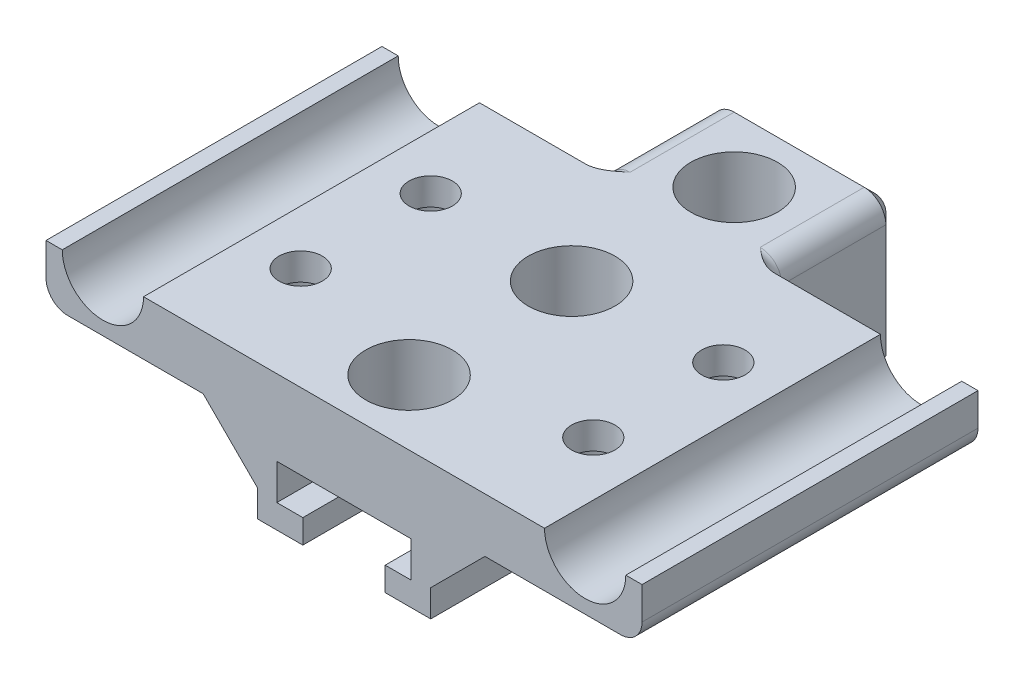
SolidWorks part; units mm, degrees
ref_plane "前基準面" through (0, 0, 0) normal (0, 0, 1) x (1, 0, 0)
ref_plane "上基準面" through (0, 0, 0) normal (0, 1, 0) x (1, 0, 0)
ref_plane "右基準面" through (0, 0, 0) normal (1, 0, 0) x (0, 0, -1)
sketch "草圖1" plane through (0, 0, 0) normal (0, 0, 1) x (1, 0, 0)
  line L1 (-8, 4) -> (8, 4)
  line L2 (-8, 4) -> (-8, -4)
  line L3 (-8, -4) -> (8, -4)
  line L4 (8, 4) -> (8, -4)
  point P4 (0, 4)
  point P7 (-8, 0)
  dimension "D1" = 16
  dimension "D2" = 8
extrude "填料-伸長1" add sketch "草圖1" along normal blind 43
sketch "草圖2" plane through (0, 0, 43) normal (0, 0, 1) x (1, 0, 0)
  line L1 (-6.2, 2) -> (6.2, 2)
  line L2 (-6.2, 2) -> (-6.2, -1.3)
  line L3 (-3.8, -4) -> (3.8, -4)
  line L4 (6.2, 2) -> (6.2, -1.3)
  line L5 (-8, -4) -> (8, -4) construction
  line L6 (-6.2, -1.3) -> (-3.8, -1.3)
  line L9 (-3.8, -1.3) -> (-3.8, -4)
  line L10 (6.2, -1.3) -> (3.8, -1.3)
  line L13 (3.8, -1.3) -> (3.8, -4)
  point P6 (0, 2)
  dimension "D1" = 12.4
  dimension "D2" = 6
  dimension "D3" = 2.4
  dimension "D4" = 2.4
  dimension "D5" = 2.7
  dimension "D6" = 2.7
  dimension "D7" = 3.3
extrude "除料-伸長1" cut sketch "草圖2" against normal through all
sketch "草圖4" plane through (0, 0, 43) normal (0, 0, 1) x (1, 0, 0)
  line L0 (8, 4) -> (-8, 4) construction
  line L1 (-27.5, 4) -> (27.5, 4)
  line L2 (-27.5, 4) -> (-27.5, 9)
  line L3 (-27.5, 9) -> (-26, 9)
  line L4 (27.5, 4) -> (27.5, 9)
  line L5 (-18.5, 9) -> (18.5, 9)
  line L6 (26, 9) -> (27.5, 9)
  arc A0 (-26, 9) -> (-18.5, 9) centre (-22.25, 9) ccw
  arc A1 (18.5, 9) -> (26, 9) centre (22.25, 9) ccw
  dimension "D3" = 7.5
  dimension "D4" = 7.5
  dimension "D1" = 55
  dimension "D2" = 5
extrude "填料-伸長2" add sketch "草圖4" against normal blind 31
fillet "圓角1" radius 2 2 edges at (-27.5, 4, 27.5) (27.5, 4, 27.5)
chamfer "導角1" distance 5 angle 45 2 edges at (8, 4, 27.5) (-8, 4, 27.5)
sketch "草圖5" plane through (0, 9, 0) normal (0, 1, 0) x (1, 0, 0)
  line L0 (-27.5, -12) -> (-27.5, -43) construction
  line L1 (27.5, -12) -> (27.5, -43) construction
  line L2 (-18.5, -27.5) -> (18.5, -27.5) construction
  line L3 (18.5, -43) -> (-18.5, -43) construction
  line L4 (-18.5, -12) -> (-18.5, -43) construction
  line L5 (18.5, -12) -> (18.5, -43) construction
  circle A0 centre (-13.5, -21.5) radius 2
  circle A1 centre (13.5, -21.5) radius 2
  circle A2 centre (13.5, -33.5) radius 2
  circle A3 centre (-13.5, -33.5) radius 2
  dimension "D1" = 4
  dimension "D2" = 4
  dimension "D3" = 14
  dimension "D4" = 14
  dimension "D5" = 21.5
  dimension "D6" = 21.5
extrude "除料-伸長3" cut sketch "草圖5" against normal through all
sketch "草圖6" plane through (0, 4, 0) normal (0, -1, 0) x (1, 0, 0)
  circle A0 centre (-13.5, 21.5) radius 3.75
  circle A1 centre (13.5, 21.5) radius 3.75
  circle A2 centre (13.5, 33.5) radius 3.75
  circle A3 centre (-13.5, 33.5) radius 3.75
  dimension "D1" = 7.5
  dimension "D2" = 7.5
  dimension "D3" = 7.5
  dimension "D4" = 7.5
extrude "除料-伸長4" cut sketch "草圖6" against normal blind 2.5 and the other way through all
sketch "草圖8" plane through (0, 0, 12) normal (0, 0, -1) x (-1, 0, 0)
  line L0 (-18.5, 9) -> (18.5, 9) construction
  line L1 (-8, 4) -> (8, 4)
  line L2 (-8, 4) -> (-8, 9)
  line L3 (-8, 9) -> (8, 9)
  line L4 (8, 4) -> (8, 9)
extrude "填料-伸長4" add sketch "草圖8" along normal up to surface (12 mm away) up to face at (0, -0.7667, 0)
sketch "草圖3" plane through (0, 9, 0) normal (0, 1, 0) x (1, 0, 0)
  circle A0 centre (0, -37) radius 4
  circle A1 centre (0, -22) radius 4
  circle A2 centre (0, -7) radius 4
  dimension "D1" = 8
  dimension "D3" = 3
extrude "除料-伸長2" cut sketch "草圖3" against normal blind 6.2
sketch "草圖10" plane through (0, 0, 43) normal (0, 0, 1) x (1, 0, 0)
  line L0 (-6.2, -1.3) -> (-3.8, -1.3) construction
  line L1 (-3.8, -4) -> (-8, -4)
  line L2 (-3.8, -4) -> (-3.8, -3.5)
  line L3 (-3.8, -3.5) -> (-8, -3.5)
  line L4 (-8, -4) -> (-8, -3.5)
  line L5 (3.8, -4) -> (8, -4)
  line L6 (3.8, -4) -> (3.8, -3.5)
  line L7 (3.8, -3.5) -> (8, -3.5)
  line L8 (8, -4) -> (8, -3.5)
  line L9 (3.8, -1.3) -> (6.2, -1.3) construction
  line L11 (-8, -1) -> (-8, -4) construction
  line L12 (8, -4) -> (8, -1) construction
  dimension "D1" = 2.2
  dimension "D2" = 2.2
extrude "除料-伸長5" cut sketch "草圖10" against normal through all
fillet "圓角2" radius 2 2 edges at (8, 9, 6) (-8, 9, 6)
chamfer "導角2" distance 1 angle 45 5 edges at (8, 1.75, 0) (-8, 1.75, 0) (7.4142, 8.4142, 0) (-7.4142, 8.4142, 0) (0, 9, 0)
fillet "圓角3" radius 1.4 4 edges at (7.4142, 8.4142, 12) (-7.4142, 8.4142, 12) (8, 3, 12) (-8, 3, 12)
sketch "草圖11" plane through (0, 0, 12) normal (0, 0, -1) x (-1, 0, 0)
  line L0 (-17.6, 5) -> (-10.6, 5) construction
  line L2 (-13, 4) -> (-25.5, 4) construction
  line L3 (-9.4, 0.4) -> (-9.4, 7) construction
  line L4 (0, 9) -> (0, 0) construction
  line L5 (-6, 9) -> (6, 9) construction
  line L6 (17.6, 5) -> (10.6, 5) construction
  line L7 (-13.6371, 7.16) -> (-13.6371, 8.2545)
  line L8 (15.5364, 7.6659) -> (16.1812, 5.9016)
  spline S0 degree 3 poles (-14.3217, 5.6792) (-14.3613, 5.5944) (-14.4274, 5.4735) (-14.525, 5.3224) (-14.5998, 5.2193) (-14.68, 5.1259) (-14.7882, 5.0123) (-14.878, 4.9386) (-14.94, 4.8946) knots 0 0 0 0 0.277898 0.408711 0.534276 0.656039 0.774144 1 1 1 1
  spline S1 degree 3 poles (-14.94, 4.8946) (-14.99, 4.8607) (-15.067, 4.8143) (-15.1749, 4.766) (-15.2555, 4.7357) (-15.3377, 4.7134) (-15.4487, 4.6913) (-15.5335, 4.6842) (-15.5902, 4.6846) knots 0 0 0 0 0.261398 0.38728 0.510792 0.633341 0.754911 1 1 1 1
  spline S2 degree 3 poles (-15.5902, 4.6846) (-15.667, 4.6851) (-15.7816, 4.6959) (-15.9282, 4.7374) (-16.0337, 4.7799) (-16.1355, 4.8345) (-16.2674, 4.9271) (-16.3577, 5.0104) (-16.413, 5.0726) knots 0 0 0 0 0.245474 0.365588 0.485789 0.608633 0.734185 1 1 1 1
  spline S3 degree 3 poles (-16.413, 5.0726) (-16.4864, 5.1498) (-16.5808, 5.2815) (-16.6806, 5.4755) (-16.74, 5.6355) (-16.7883, 5.8066) (-16.8331, 6.0584) (-16.8454, 6.2551) (-16.8455, 6.3895) knots 0 0 0 0 0.22456 0.340653 0.460058 0.584555 0.715943 1 1 1 1
  spline S4 degree 3 poles (-16.8455, 6.3895) (-16.8458, 6.523) (-16.8373, 6.7183) (-16.8036, 6.97) (-16.7682, 7.1431) (-16.7243, 7.3059) (-16.6528, 7.5051) (-16.5817, 7.6438) (-16.5278, 7.7299) knots 0 0 0 0 0.286836 0.419499 0.545655 0.666292 0.781656 1 1 1 1
  spline S5 degree 3 poles (-16.5278, 7.7299) (-16.4753, 7.8088) (-16.3891, 7.9209) (-16.2476, 8.0391) (-16.136, 8.1114) (-16.015, 8.166) (-15.84, 8.2208) (-15.7001, 8.234) (-15.6059, 8.2342) knots 0 0 0 0 0.259167 0.381557 0.501242 0.62064 0.742518 1 1 1 1
  spline S6 degree 3 poles (-15.6059, 8.2342) (-15.5447, 8.234) (-15.4227, 8.2202) (-15.3072, 8.1784) (-15.253, 8.1507) knots 0 0 0 0 0.501439 1 1 1 1
  spline S7 degree 3 poles (-15.253, 8.1507) (-15.2323, 8.1338) (-15.2068, 8.1071) (-15.174, 8.077) (-15.1582, 8.0594) (-15.1475, 8.0463) (-15.1417, 8.0391) (-15.1407, 8.0355) knots 0 0 0 0 0.465485 0.641944 0.776824 0.876731 0.937633 0.937633 0.937633 0.937633
  spline S8 degree 3 poles (-15.1407, 8.0355) (-15.1338, 8.0444) (-15.1164, 8.0704) (-15.0772, 8.1526) (-15.0487, 8.2267) (-15.0282, 8.2826) knots 0.030175 0.030175 0.030175 0.030175 0.149661 0.364791 1 1 1 1
  spline S9 degree 3 poles (-15.0282, 8.2826) (-15.0097, 8.2769) (-14.9811, 8.2614) (-14.9432, 8.232) (-14.9076, 8.2019) (-14.8684, 8.1648) (-14.8077, 8.1023) (-14.7606, 8.0515) (-14.7292, 8.0141) knots 0 0 0 0 0.142547 0.238878 0.355068 0.487277 0.638501 1 1 1 1
  spline S10 degree 3 poles (-14.7292, 8.0141) (-14.6798, 7.9548) (-14.5966, 7.8461) (-14.5548, 7.7149) (-14.5543, 7.6565) knots 0 0 0 0 0.573162 1 1 1 1
  spline S11 degree 3 poles (-14.5543, 7.6565) (-14.5557, 7.6048) (-14.5593, 7.5297) (-14.5908, 7.4416) (-14.6204, 7.3896) (-14.6607, 7.3494) (-14.7286, 7.3093) (-14.7899, 7.3016) (-14.8307, 7.3013) knots 0 0 0 0 0.30493 0.430936 0.544107 0.651621 0.759317 1 1 1 1
  spline S12 degree 3 poles (-14.8307, 7.3013) (-14.8415, 7.3023) (-14.8603, 7.3108) (-14.8897, 7.3261) (-14.9229, 7.3449) (-14.9637, 7.3682) (-15.0323, 7.4103) (-15.0873, 7.4446) (-15.1265, 7.4692) knots 0 0 0 0 0.094521 0.179485 0.292196 0.4296 0.592894 1 1 1 1
  spline S13 degree 3 poles (-15.1265, 7.4692) (-15.2, 7.5142) (-15.3438, 7.5865) (-15.5021, 7.6163) (-15.5754, 7.6167) knots 0 0 0 0 0.541453 1 1 1 1
  spline S14 degree 3 poles (-15.5754, 7.6167) (-15.6158, 7.6166) (-15.677, 7.6078) (-15.7525, 7.5748) (-15.8068, 7.5407) (-15.8586, 7.4974) (-15.9263, 7.4231) (-15.9695, 7.3578) (-15.9962, 7.3107) knots 0 0 0 0 0.221792 0.333702 0.449768 0.572417 0.702736 1 1 1 1
  spline S15 degree 3 poles (-15.9962, 7.3107) (-16.0277, 7.2575) (-16.0642, 7.1689) (-16.1026, 7.0426) (-16.1267, 6.9356) (-16.1452, 6.8196) (-16.1629, 6.6471) (-16.169, 6.513) (-16.1679, 6.4208) knots 0 0 0 0 0.201775 0.313153 0.432066 0.560726 0.697893 1 1 1 1
  spline S16 degree 3 poles (-16.1679, 6.4208) (-16.1668, 6.3257) (-16.1626, 6.1873) (-16.1377, 6.0102) (-16.1131, 5.8914) (-16.0813, 5.7824) (-16.0306, 5.6538) (-15.9805, 5.5661) (-15.9408, 5.5144) knots 0 0 0 0 0.300346 0.436413 0.56404 0.683112 0.794491 1 1 1 1
  spline S17 degree 3 poles (-15.9408, 5.5144) (-15.9107, 5.4743) (-15.8632, 5.4185) (-15.7917, 5.3566) (-15.7388, 5.3196) (-15.6842, 5.291) (-15.6101, 5.2638) (-15.5518, 5.2548) (-15.513, 5.2553) knots 0 0 0 0 0.290049 0.421162 0.545442 0.662452 0.776131 1 1 1 1
  spline S18 degree 3 poles (-15.513, 5.2553) (-15.4147, 5.2542) (-15.2665, 5.2697) (-15.0706, 5.3126) (-14.9222, 5.3603) (-14.7724, 5.4199) (-14.567, 5.5187) (-14.4196, 5.6126) (-14.3217, 5.6792) knots 0 0 0 0 0.229159 0.346857 0.467982 0.592948 0.723185 1 1 1 1
  spline S19 degree 3 poles (-11.3818, 7.6721) (-11.3817, 7.6685) (-11.3828, 7.6599) (-11.3845, 7.6446) (-11.3855, 7.6237) (-11.3895, 7.597) (-11.3915, 7.5484) (-11.3977, 7.5094) (-11.399, 7.4809) knots 0 0 0 0 0.05709 0.134746 0.24074 0.38393 0.555081 1 1 1 1
  spline S20 degree 2 poles (-11.399, 7.4809) (-11.4138, 7.3247) (-11.42, 7.1678) knots 0 0 0 1 1 1
  spline S21 degree 3 poles (-11.42, 7.1678) (-11.4294, 6.9098) (-11.4395, 6.3779) (-11.4446, 5.846) (-11.4442, 5.5722) knots 0 0 0 0 0.485385 1 1 1 1
  spline S22 degree 3 poles (-11.4442, 5.5722) (-11.4452, 5.4586) (-11.4547, 5.2494) (-11.5073, 5.0464) (-11.5426, 4.9586) knots 0 0 0 0 0.546328 1 1 1 1
  spline S23 degree 3 poles (-11.5426, 4.9586) (-11.5576, 4.9111) (-11.5797, 4.8432) (-11.6232, 4.7646) (-11.6565, 4.7186) (-11.6935, 4.6825) (-11.7471, 4.6489) (-11.7923, 4.6364) (-11.8229, 4.6378) knots 0 0 0 0 0.328144 0.464958 0.588231 0.699329 0.802126 1 1 1 1
  spline S24 degree 3 poles (-11.8229, 4.6378) (-11.847, 4.6374) (-11.8843, 4.6477) (-11.9302, 4.6754) (-11.9669, 4.7048) (-12.0046, 4.7417) (-12.0419, 4.7876) (-12.0802, 4.8417) (-12.1185, 4.9041) (-12.1592, 4.9738) (-12.1979, 5.053) (-12.24, 5.1394) (-12.2807, 5.2348) (-12.3232, 5.3381) (-12.3819, 5.4917) (-12.425, 5.6116) (-12.4521, 5.6948) knots 0 0 0 0 0.056453 0.089168 0.125855 0.167059 0.213234 0.26514 0.323002 0.385916 0.455312 0.530755 0.612338 0.699811 0.793782 1 1 1 1
  spline S25 degree 3 poles (-12.4521, 5.6948) (-12.4145, 5.6815) (-12.3597, 5.666) (-12.2913, 5.6441) (-12.2475, 5.6337) (-12.21, 5.6238) (-12.1707, 5.6163) (-12.1441, 5.6125) (-12.1281, 5.612) knots 0 0 0 0 0.356585 0.509865 0.642066 0.759578 0.856884 1 1 1 1
  spline S26 degree 3 poles (-12.1281, 5.612) (-12.1173, 5.6118) (-12.0934, 5.6229) (-12.0827, 5.647) (-12.0774, 5.6596) knots 0 0 0 0 0.428656 1 1 1 1
  spline S27 degree 3 poles (-12.0774, 5.6596) (-12.0674, 5.7001) (-12.0539, 5.8107) (-12.0553, 5.922) (-12.0539, 5.9914) knots 0 0 0 0 0.374326 1 1 1 1
  spline S28 degree 3 poles (-12.0539, 5.9914) (-12.0542, 6.019) (-12.053, 6.071) (-12.0523, 6.1543) (-12.0517, 6.248) (-12.0498, 6.3622) (-12.049, 6.4529) (-12.0483, 6.5057) (-12.0482, 6.5134) knots 0 0 0 0 0.099436 0.187614 0.30018 0.437142 0.599429 0.627202 0.627202 0.627202 0.627202
  spline S29 degree 3 poles (-12.0438, 6.8236) (-12.0429, 6.9344) (-12.0395, 7.0903) (-12.0378, 7.2839) (-12.0359, 7.3974) (-12.0353, 7.4895) (-12.0346, 7.5701) (-12.0333, 7.6201) (-12.0336, 7.6464) knots 0 0 0 0 0.404182 0.568316 0.70589 0.817839 0.904175 1 1 1 1
  spline S30 degree 3 poles (-12.0336, 7.6464) (-12.0349, 7.676) (-12.0335, 7.7172) (-12.0373, 7.768) (-12.04, 7.7964) (-12.044, 7.8189) (-12.0486, 7.8371) (-12.0544, 7.8483) (-12.061, 7.8494) knots 0 0 0 0 0.424717 0.588998 0.727627 0.833577 0.914933 1 1 1 1
  spline S31 degree 3 poles (-12.061, 7.8494) (-12.0598, 7.844) (-12.0754, 7.8404) (-12.0929, 7.8284) (-12.1237, 7.8144) (-12.1624, 7.7956) (-12.2332, 7.7611) (-12.2913, 7.7342) (-12.3334, 7.7151) knots 0 0 0 0 0.046726 0.118815 0.227506 0.369395 0.545604 1 1 1 1
  spline S32 degree 3 poles (-12.3334, 7.7151) (-12.3038, 7.7918) (-12.2616, 7.9007) (-12.1899, 8.0281) (-12.1409, 8.1021) (-12.0905, 8.1598) (-12.0258, 8.2131) (-11.9697, 8.2354) (-11.9322, 8.2342) knots 0 0 0 0 0.358944 0.507248 0.636248 0.745525 0.839951 1 1 1 1
  spline S33 degree 3 poles (-11.9322, 8.2342) (-11.901, 8.2335) (-11.8533, 8.229) (-11.793, 8.2073) (-11.7478, 8.1863) (-11.7026, 8.1596) (-11.6429, 8.1127) (-11.6011, 8.0715) (-11.5746, 8.0414) knots 0 0 0 0 0.223862 0.338171 0.457372 0.581032 0.712582 1 1 1 1
  spline S34 degree 3 poles (-11.5746, 8.0414) (-11.5439, 8.01) (-11.5045, 7.9606) (-11.4566, 7.8949) (-11.43, 7.8475) (-11.4092, 7.8017) (-11.3876, 7.7447) (-11.3826, 7.7005) (-11.3818, 7.6721) knots 0 0 0 0 0.308572 0.445382 0.571802 0.690744 0.799749 1 1 1 1
  spline S35 degree 3 poles (-12.0482, 6.5134) (-12.0485, 6.5132) (-12.0646, 6.5062) (-12.1202, 6.4831) (-12.1778, 6.4664) (-12.2186, 6.4543) knots 0.450889 0.450889 0.450889 0.450889 0.454476 0.610995 1 1 1 1
  spline S36 degree 3 poles (-12.2186, 6.4543) (-12.2999, 6.4337) (-12.4141, 6.4072) (-12.555, 6.3725) (-12.6364, 6.3546) (-12.7006, 6.3381) (-12.7538, 6.3272) (-12.7853, 6.3207) (-12.801, 6.3185) knots 0 0 0 0 0.420418 0.588208 0.727522 0.838959 0.920368 1 1 1 1
  spline S37 degree 3 poles (-12.801, 6.3185) (-12.8263, 6.318) (-12.865, 6.3256) (-12.9134, 6.3486) (-12.95, 6.3733) (-12.987, 6.404) (-13.0381, 6.4568) (-13.0726, 6.503) (-13.0945, 6.5363) knots 0 0 0 0 0.199082 0.305665 0.421303 0.54674 0.684715 1 1 1 1
  spline S38 degree 3 poles (-13.0945, 6.5363) (-13.0989, 6.4589) (-13.1095, 6.332) (-13.1214, 6.1863) (-13.1275, 6.118) (-13.1292, 6.0993) knots 0 0 0 0 0.419765 0.689913 0.79148 0.79148 0.79148 0.79148
  spline S39 degree 3 poles (-13.1292, 6.0993) (-13.1241, 6.1062) (-13.1052, 6.1299) (-13.0461, 6.1943) (-12.9871, 6.2469) (-12.9439, 6.2842) knots 0.343319 0.343319 0.343319 0.343319 0.407546 0.57092 1 1 1 1
  spline S40 degree 3 poles (-12.9439, 6.2842) (-12.9775, 6.155) (-13.0215, 5.9672) (-13.0735, 5.7252) (-13.1027, 5.5639) (-13.1268, 5.4164) (-13.1475, 5.2469) (-13.1565, 5.1262) (-13.1562, 5.05) knots 0 0 0 0 0.319114 0.460875 0.591788 0.710824 0.817991 1 1 1 1
  spline S41 degree 3 poles (-13.1562, 5.05) (-13.1575, 4.9967) (-13.1588, 4.9209) (-13.1814, 4.8299) (-13.2019, 4.7776) (-13.2287, 4.7356) (-13.2747, 4.6955) (-13.3195, 4.6837) (-13.349, 4.6846) knots 0 0 0 0 0.348333 0.48797 0.608721 0.712514 0.808573 1 1 1 1
  spline S42 degree 3 poles (-13.349, 4.6846) (-13.3761, 4.6839) (-13.4169, 4.6988) (-13.4641, 4.7359) (-13.4999, 4.776) (-13.5361, 4.8261) (-13.5839, 4.9153) (-13.6164, 4.9889) (-13.6347, 5.0429) knots 0 0 0 0 0.16568 0.261563 0.371599 0.499247 0.645699 1 1 1 1
  spline S43 degree 3 poles (-13.6347, 5.0429) (-13.67, 5.1466) (-13.7231, 5.3485) (-13.7459, 5.5562) (-13.7456, 5.655) knots 0 0 0 0 0.526101 1 1 1 1
  spline S44 degree 3 poles (-13.7456, 5.655) (-13.7458, 5.6826) (-13.7417, 5.7317) (-13.7378, 5.808) (-13.7313, 5.8887) (-13.7222, 5.9849) (-13.7097, 6.1445) (-13.6966, 6.2719) (-13.6886, 6.3622) knots 0 0 0 0 0.116756 0.208224 0.322966 0.45881 0.616668 1 1 1 1
  spline S45 degree 3 poles (-13.6886, 6.3622) (-13.682, 6.4534) (-13.669, 6.5838) (-13.6579, 6.75) (-13.6495, 6.8558) (-13.6442, 6.9492) (-13.6393, 7.0491) (-13.6372, 7.1181) (-13.6371, 7.16) knots 0 0 0 0 0.342852 0.491627 0.624753 0.741125 0.842771 1 1 1 1
  spline S46 degree 3 poles (-13.6371, 8.2545) (-13.5758, 8.2154) (-13.4894, 8.1602) (-13.3821, 8.0899) (-13.3184, 8.0471) (-13.2656, 8.0112) (-13.2176, 7.9765) (-13.1867, 7.9541) (-13.171, 7.9399) knots 0 0 0 0 0.387621 0.546962 0.683977 0.796754 0.887252 1 1 1 1
  spline S47 degree 3 poles (-13.171, 7.9399) (-13.1417, 7.9095) (-13.1033, 7.8619) (-13.0644, 7.7943) (-13.0451, 7.7462) (-13.0349, 7.6989) (-13.0312, 7.637) (-13.0422, 7.5916) (-13.0547, 7.5636) knots 0 0 0 0 0.302895 0.435634 0.557849 0.672309 0.780589 1 1 1 1
  spline S48 degree 3 poles (-13.0547, 7.5636) (-13.0625, 7.5601) (-13.0712, 7.5476) (-13.0791, 7.5264) (-13.0844, 7.5024) (-13.0879, 7.4726) (-13.0909, 7.4367) (-13.0934, 7.395) (-13.0938, 7.3474) (-13.0938, 7.2941) (-13.0932, 7.2344) (-13.0905, 7.1691) (-13.0877, 7.0978) (-13.0826, 7.0206) (-13.0756, 6.9055) (-13.0672, 6.8163) (-13.0625, 6.7549) knots 0 0 0 0 0.03015 0.053694 0.083059 0.119595 0.16361 0.215164 0.272367 0.338141 0.410594 0.490717 0.577546 0.672091 0.774306 1 1 1 1
  spline S49 degree 3 poles (-13.0625, 6.7549) (-13.0456, 6.7599) (-13.0179, 6.7701) (-12.9771, 6.7852) (-12.9377, 6.8001) (-12.8929, 6.8181) (-12.8215, 6.8466) (-12.7653, 6.8693) (-12.7261, 6.8853) knots 0 0 0 0 0.146408 0.245649 0.361347 0.496307 0.647736 1 1 1 1
  spline S50 degree 3 poles (-12.7261, 6.8853) (-12.6881, 6.8993) (-12.6349, 6.9193) (-12.5687, 6.943) (-12.5303, 6.956) (-12.4998, 6.9673) (-12.4736, 6.9762) (-12.4573, 6.9806) (-12.4489, 6.9828) knots 0 0 0 0 0.413502 0.579857 0.717628 0.827698 0.911698 1 1 1 1
  spline S51 degree 3 poles (-12.4489, 6.9828) (-12.3839, 6.9825) (-12.2476, 6.9557) (-12.1378, 6.8706) (-12.0883, 6.822) knots 0 0 0 0 0.482707 1 1 1 1
  spline S52 degree 2 poles (-12.0883, 6.822) (-12.0659, 6.7986) (-12.0443, 6.7746) knots 0 0 0 0.244225 0.244225 0.244225
  spline S53 degree 3 poles (16.8697, 7.7908) (16.8683, 7.771) (16.8558, 7.7083) (16.841, 7.6463) (16.8307, 7.6034) knots 0 0 0 0 0.309803 1 1 1 1
  spline S54 degree 3 poles (16.8307, 7.6034) (16.8218, 7.5656) (16.8091, 7.4956) (16.8023, 7.4248) (16.8026, 7.3927) knots 0 0 0 0 0.547805 1 1 1 1
  spline S55 degree 3 poles (16.8026, 7.3927) (16.8028, 7.3549) (16.8024, 7.2927) (16.7998, 7.2025) (16.7997, 7.1179) (16.7979, 7.0221) (16.7944, 6.8723) (16.7924, 6.7544) (16.7909, 6.6721) knots 0 0 0 0 0.15708 0.258929 0.375926 0.509185 0.657628 1 1 1 1
  spline S56 degree 3 poles (16.7909, 6.6721) (16.7896, 6.5876) (16.7868, 6.4645) (16.7844, 6.3052) (16.7842, 6.197) (16.7821, 6.0963) (16.7812, 5.9768) (16.7817, 5.891) (16.7815, 5.8361) knots 0 0 0 0 0.30348 0.44167 0.571447 0.691899 0.803005 1 1 1 1
  spline S57 degree 3 poles (16.7815, 5.8361) (16.7827, 5.746) (16.7789, 5.6156) (16.7723, 5.4477) (16.7633, 5.3353) (16.7535, 5.2317) (16.7415, 5.137) (16.7254, 5.0518) (16.7087, 4.975) (16.6895, 4.9071) (16.6679, 4.8482) (16.6437, 4.7984) (16.6175, 4.7572) (16.5882, 4.7252) (16.5469, 4.6942) (16.5097, 4.6848) (16.4856, 4.6846) knots 0 0 0 0 0.214683 0.310932 0.40052 0.483417 0.55913 0.627875 0.69018 0.746333 0.795994 0.83955 0.878091 0.911892 0.94254 1 1 1 1
  spline S58 degree 3 poles (16.4856, 4.6846) (16.4718, 4.6853) (16.4497, 4.6936) (16.4196, 4.7118) (16.3917, 4.7335) (16.3596, 4.7598) (16.3097, 4.8069) (16.2726, 4.8471) (16.246, 4.8751) knots 0 0 0 0 0.13189 0.225383 0.338432 0.47224 0.626877 1 1 1 1
  spline S59 degree 3 poles (16.246, 4.8751) (16.2057, 4.9179) (16.1354, 4.9928) (16.0715, 5.0734) (16.0461, 5.1093) knots 0 0 0 0 0.572146 1 1 1 1
  spline S60 degree 3 poles (16.0461, 5.1093) (16.0008, 5.1736) (15.9147, 5.3133) (15.8457, 5.4622) (15.8135, 5.541) knots 0 0 0 0 0.480311 1 1 1 1
  spline S61 degree 3 poles (15.8135, 5.541) (15.7735, 5.6321) (15.7135, 5.7806) (15.6358, 5.9951) (15.5687, 6.1876) (15.4977, 6.4018) (15.3937, 6.7303) (15.3153, 6.988) (15.2616, 7.1671) knots 0 0 0 0 0.173657 0.279594 0.398429 0.529611 0.673594 1 1 1 1
  spline S62 degree 3 poles (15.2616, 7.1671) (15.2632, 7.1359) (15.2639, 7.0854) (15.2645, 7.0135) (15.2667, 6.949) (15.267, 6.8777) (15.2679, 6.7991) (15.2687, 6.7138) (15.2694, 6.6214) (15.2705, 6.5223) (15.2698, 6.4161) (15.2714, 6.3029) (15.2706, 6.1827) (15.2721, 6.0554) (15.2715, 5.872) (15.2719, 5.7309) (15.2717, 5.6347) knots 0 0 0 0 0.06115 0.098849 0.140632 0.187499 0.238441 0.294477 0.354588 0.419284 0.488562 0.562426 0.640873 0.723907 0.811523 1 1 1 1
  spline S63 degree 3 poles (15.2717, 5.6347) (15.2719, 5.5605) (15.2706, 5.4527) (15.2628, 5.3143) (15.256, 5.2213) (15.2469, 5.1359) (15.2351, 5.0578) (15.2221, 4.9871) (15.2068, 4.9239) (15.1886, 4.8683) (15.1697, 4.8195) (15.1475, 4.7787) (15.1246, 4.7443) (15.0983, 4.7179) (15.0609, 4.6922) (15.0278, 4.685) (15.0063, 4.6846) knots 0 0 0 0 0.211935 0.307985 0.395969 0.478236 0.553415 0.621511 0.683541 0.739028 0.78873 0.832639 0.87162 0.906317 0.938485 1 1 1 1
  spline S64 degree 3 poles (15.0063, 4.6846) (14.9868, 4.6844) (14.9567, 4.6958) (14.9197, 4.7228) (14.8888, 4.753) (14.8558, 4.7907) (14.8074, 4.857) (14.7721, 4.912) (14.7495, 4.9524) knots 0 0 0 0 0.150367 0.245396 0.357869 0.48789 0.63793 1 1 1 1
  spline S65 degree 3 poles (14.7495, 4.9524) (14.7093, 5.0263) (14.6458, 5.1573) (14.6098, 5.2991) (14.6098, 5.3607) knots 0 0 0 0 0.579954 1 1 1 1
  spline S66 degree 3 poles (14.6098, 5.3607) (14.6106, 5.3718) (14.6122, 5.3947) (14.6144, 5.4336) (14.62, 5.4808) (14.6238, 5.5405) (14.6337, 5.6443) (14.6396, 5.7284) (14.6457, 5.7885) knots 0 0 0 0 0.078379 0.160387 0.271842 0.410467 0.578387 1 1 1 1
  spline S67 degree 3 poles (14.6457, 5.7885) (14.6592, 5.9255) (14.6755, 6.2052) (14.6827, 6.4852) (14.6824, 6.6276) knots 0 0 0 0 0.491659 1 1 1 1
  spline S68 degree 3 poles (14.6824, 6.6276) (14.6824, 6.7112) (14.6824, 6.8275) (14.6824, 6.9709) (14.6824, 7.0515) (14.6824, 7.1142) (14.6824, 7.1619) (14.6824, 7.1887) (14.6824, 7.2006) knots 0 0 0 0 0.43733 0.608992 0.750681 0.859673 0.93733 1 1 1 1
  spline S69 degree 3 poles (14.6824, 7.2006) (14.6787, 7.3059) (14.6668, 7.5091) (14.6389, 7.7108) (14.6207, 7.8072) knots 0 0 0 0 0.517943 1 1 1 1
  spline S70 degree 3 poles (14.6207, 7.8072) (14.6099, 7.8633) (14.5488, 7.9843) (14.4575, 8.0832) (14.4029, 8.1374) knots 0 0 0 0 0.423241 1 1 1 1
  spline S71 degree 2 poles (14.4029, 8.1374) (14.5503, 8.1698) (14.7011, 8.1718) knots 0 0 0 1 1 1
  spline S72 degree 3 poles (14.7011, 8.1718) (14.7958, 8.1715) (14.9349, 8.1593) (15.1064, 8.1044) (15.2188, 8.0489) (15.3179, 7.9764) (15.4363, 7.8567) (15.5024, 7.7457) (15.5364, 7.6659) knots 0 0 0 0 0.273498 0.397956 0.516968 0.632872 0.750017 1 1 1 1
  spline S73 degree 3 poles (16.1812, 5.9016) (16.1834, 6.0115) (16.1881, 6.1725) (16.192, 6.3825) (16.1951, 6.5295) (16.1985, 6.6695) (16.2006, 6.8025) (16.2029, 6.9285) (16.2055, 7.0474) (16.2069, 7.1595) (16.2084, 7.2644) (16.2104, 7.3625) (16.2104, 7.4533) (16.213, 7.5373) (16.212, 7.6141) (16.2131, 7.6713) (16.2134, 7.7027) (16.2134, 7.711) knots 0 0 0 0 0.178304 0.261535 0.340965 0.417016 0.488836 0.556855 0.621495 0.681905 0.738936 0.791743 0.841166 0.886371 0.928189 0.965785 0.979193 0.979193 0.979193 0.979193
  spline S76 degree 3 poles (16.2134, 7.711) (16.1989, 7.7258) (16.1691, 7.7581) (16.1271, 7.8067) (16.0864, 7.8522) (16.0546, 7.8937) (16.0291, 7.9296) (16.0075, 7.9662) (15.9974, 7.9926) (15.9962, 8.0086) knots 0.041806 0.041806 0.041806 0.041806 0.201741 0.381039 0.537668 0.672245 0.784786 0.877456 1 1 1 1
  spline S77 degree 3 poles (15.9962, 8.0086) (15.9965, 8.0364) (16.0205, 8.0978) (16.0676, 8.1433) (16.0945, 8.1679) knots 0 0 0 0 0.426406 1 1 1 1
  spline S78 degree 3 poles (16.0945, 8.1679) (16.1234, 8.1876) (16.1782, 8.2191) (16.2398, 8.2348) (16.2678, 8.2342) knots 0 0 0 0 0.557784 1 1 1 1
  spline S79 degree 3 poles (16.2678, 8.2342) (16.3207, 8.2343) (16.4393, 8.2031) (16.5462, 8.1441) (16.6043, 8.107) knots 0 0 0 0 0.431331 1 1 1 1
  spline S80 degree 3 poles (16.6043, 8.107) (16.6439, 8.0822) (16.7013, 8.0468) (16.7648, 7.9901) (16.8034, 7.9514) (16.8324, 7.9112) (16.8604, 7.8597) (16.8703, 7.818) (16.8697, 7.7908) knots 0 0 0 0 0.326782 0.46693 0.592702 0.707036 0.81175 1 1 1 1
  spline S81 degree 3 poles (13.7799, 4.9984) (13.7795, 4.9744) (13.7758, 4.9379) (13.7522, 4.8981) (13.7295, 4.8742) (13.6997, 4.8564) (13.6491, 4.8375) (13.6059, 4.8345) (13.5762, 4.8345) knots 0 0 0 0 0.245261 0.354229 0.459626 0.573532 0.699302 1 1 1 1
  spline S82 degree 3 poles (13.5762, 4.8345) (13.5504, 4.8357) (13.4696, 4.8497) (13.3893, 4.8652) (13.3342, 4.8759) knots 0 0 0 0 0.314363 1 1 1 1
  spline S83 degree 3 poles (13.3342, 4.8759) (13.2589, 4.8882) (13.0936, 4.9088) (12.9269, 4.9108) (12.8369, 4.9118) knots 0 0 0 0 0.458517 1 1 1 1
  spline S84 degree 3 poles (12.8369, 4.9118) (12.7539, 4.9118) (12.6331, 4.9094) (12.4777, 4.8961) (12.3726, 4.8843) (12.2752, 4.8675) (12.1596, 4.843) (12.078, 4.8172) (12.0274, 4.7963) knots 0 0 0 0 0.302959 0.440119 0.569159 0.688536 0.800245 1 1 1 1
  spline S85 degree 3 poles (12.0274, 4.7963) (12.0141, 4.7904) (11.9726, 4.7624) (11.9297, 4.7371) (11.9001, 4.7174) knots 0 0 0 0 0.289956 1 1 1 1
  spline S86 degree 3 poles (11.9001, 4.7174) (11.8641, 4.6992) (11.8083, 4.6742) (11.7509, 4.6517) (11.73, 4.6487) knots 0 0 0 0 0.657092 1 1 1 1
  spline S87 degree 3 poles (11.73, 4.6487) (11.7154, 4.6482) (11.6943, 4.659) (11.6677, 4.6808) (11.6457, 4.706) (11.6221, 4.7377) (11.5866, 4.7927) (11.5613, 4.8386) (11.545, 4.872) knots 0 0 0 0 0.140548 0.231431 0.344122 0.474596 0.627311 1 1 1 1
  spline S88 degree 3 poles (11.545, 4.872) (11.5302, 4.9015) (11.5117, 4.9444) (11.4954, 5.0006) (11.4897, 5.0357) (11.4891, 5.0667) (11.4963, 5.101) (11.5088, 5.1233) (11.5223, 5.1327) knots 0 0 0 0 0.35414 0.49901 0.626074 0.734888 0.82901 1 1 1 1
  spline S89 degree 3 poles (11.5223, 5.1327) (11.5357, 5.134) (11.5517, 5.1511) (11.5586, 5.1839) (11.5608, 5.2191) (11.5565, 5.2635) (11.547, 5.3417) (11.5302, 5.4039) (11.5208, 5.4489) knots 0 0 0 0 0.111323 0.190906 0.295837 0.426461 0.588358 1 1 1 1
  spline S90 degree 3 poles (11.5208, 5.4489) (11.5357, 5.5084) (11.5532, 5.6012) (11.5715, 5.7294) (11.5832, 5.8333) (11.5916, 5.9427) (11.6, 6.099) (11.6025, 6.2193) (11.6027, 6.3013) knots 0 0 0 0 0.214283 0.330049 0.452688 0.57951 0.71341 1 1 1 1
  spline S91 degree 2 poles (11.6027, 6.3013) (11.6028, 6.496) (11.5871, 6.6901) knots 0 0 0 1 1 1
  spline S92 degree 3 poles (11.5871, 6.6901) (11.582, 6.7426) (11.5773, 6.8235) (11.5714, 6.9045) (11.5715, 6.9329) knots 0 0 0 0 0.649872 1 1 1 1
  spline S93 degree 3 poles (11.5715, 6.9329) (11.5709, 7.0058) (11.5816, 7.1124) (11.6194, 7.2463) (11.6601, 7.3355) (11.7107, 7.4176) (11.7964, 7.5166) (11.8764, 7.576) (11.9337, 7.6097) knots 0 0 0 0 0.270679 0.395517 0.515381 0.633955 0.752561 1 1 1 1
  spline S94 degree 3 poles (11.9337, 7.6097) (11.8957, 7.6373) (11.8412, 7.6813) (11.7843, 7.7523) (11.7475, 7.8064) (11.7185, 7.8647) (11.6892, 7.9479) (11.6778, 8.0139) (11.6753, 8.0586) knots 0 0 0 0 0.263307 0.387339 0.507956 0.628292 0.7502 1 1 1 1
  spline S95 degree 3 poles (11.6753, 8.0586) (11.7349, 8.0449) (11.8618, 8.0282) (11.9895, 8.0215) (12.0563, 8.0219) knots 0 0 0 0 0.478007 1 1 1 1
  spline S96 degree 3 poles (12.0563, 8.0219) (12.1512, 8.022) (12.3677, 8.0431) (12.5816, 8.0817) (12.7011, 8.1085) knots 0 0 0 0 0.43638 1 1 1 1
  spline S97 degree 3 poles (12.7011, 8.1085) (12.782, 8.1279) (12.8954, 8.1516) (13.0344, 8.1837) (13.1126, 8.2021) (13.1738, 8.2143) (13.2198, 8.2265) (13.2462, 8.2307) (13.2577, 8.2342) knots 0 0 0 0 0.437439 0.608678 0.750387 0.859598 0.936913 1 1 1 1
  spline S98 degree 3 poles (13.2577, 8.2342) (13.3017, 8.2352) (13.3892, 8.2187) (13.4646, 8.1711) (13.4958, 8.1405) knots 0 0 0 0 0.501874 1 1 1 1
  spline S99 degree 3 poles (13.4958, 8.1405) (13.5275, 8.1081) (13.5784, 8.0441) (13.604, 7.966) (13.6043, 7.9305) knots 0 0 0 0 0.565159 1 1 1 1
  spline S100 degree 3 poles (13.6043, 7.9305) (13.6059, 7.8891) (13.5897, 7.8274) (13.5388, 7.7603) (13.4851, 7.7194) (13.4174, 7.6861) (13.2998, 7.6486) (13.2014, 7.6378) (13.132, 7.6323) knots 0 0 0 0 0.199536 0.297671 0.403654 0.523807 0.66182 1 1 1 1
  spline S101 degree 3 poles (13.132, 7.6323) (13.1186, 7.6317) (13.0958, 7.628) (13.062, 7.6201) (13.0278, 7.6126) (12.9881, 7.6021) (12.9233, 7.5857) (12.8722, 7.5711) (12.8361, 7.5605) knots 0 0 0 0 0.131954 0.226409 0.34198 0.476782 0.630225 1 1 1 1
  spline S102 degree 3 poles (12.8361, 7.5605) (12.7658, 7.5422) (12.6384, 7.5113) (12.5153, 7.4665) (12.4614, 7.445) knots 0 0 0 0 0.556368 1 1 1 1
  spline S103 degree 3 poles (12.4614, 7.445) (12.4311, 7.4365) (12.3935, 7.4174) (12.353, 7.4059) (12.3436, 7.4013) knots 0 0 0 0 0.748422 1 1 1 1
  spline S104 degree 2 poles (12.3436, 7.4013) (12.2825, 7.4028) (12.228, 7.4309) knots 0 0 0 1 1 1
  spline S105 degree 2 poles (12.228, 7.4309) (12.2064, 7.4466) (12.1804, 7.4512) knots 0 0 0 1 1 1
  spline S106 degree 3 poles (12.1804, 7.4512) (12.1779, 7.4475) (12.1671, 7.4313) (12.1499, 7.4206) (12.1414, 7.4083) knots 0 0 0 0 0.230997 1 1 1 1
  spline S107 degree 3 poles (12.1414, 7.4083) (12.1284, 7.3953) (12.1106, 7.3521) (12.1108, 7.306) (12.1094, 7.2787) knots 0 0 0 0 0.395479 1 1 1 1
  spline S108 degree 3 poles (12.1094, 7.2787) (12.1117, 7.2439) (12.1308, 7.1468) (12.1608, 7.0528) (12.1781, 6.9914) knots 0 0 0 0 0.353399 1 1 1 1
  spline S109 degree 3 poles (12.1781, 6.9914) (12.1877, 6.9532) (12.2021, 6.8993) (12.2172, 6.8314) (12.227, 6.7907) (12.2338, 6.7562) (12.2394, 6.7284) (12.2422, 6.7116) (12.2429, 6.7041) (12.243, 6.7037) knots 0 0 0 0 0.383331 0.541598 0.676551 0.790122 0.882864 0.951886 0.955969 0.955969 0.955969 0.955969
  spline S111 degree 3 poles (12.243, 6.7037) (12.2497, 6.7039) (12.2693, 6.7052) (12.3037, 6.7094) (12.3481, 6.7185) (12.3991, 6.7303) (12.4567, 6.7451) (12.5467, 6.7705) (12.6171, 6.7923) (12.666, 6.8088) knots 0.02468 0.02468 0.02468 0.02468 0.069804 0.155846 0.257026 0.373294 0.506454 0.65489 1 1 1 1
  spline S112 degree 3 poles (12.666, 6.8088) (12.7166, 6.8242) (12.7868, 6.8479) (12.8741, 6.8748) (12.9241, 6.8904) (12.9635, 6.903) (12.9956, 6.9124) (13.0143, 6.918) (13.0235, 6.9204) knots 0 0 0 0 0.42446 0.592549 0.732292 0.843689 0.924135 1 1 1 1
  spline S113 degree 3 poles (13.0235, 6.9204) (13.0778, 6.9207) (13.1931, 6.8937) (13.2882, 6.8236) (13.3334, 6.7822) knots 0 0 0 0 0.467495 1 1 1 1
  spline S114 degree 3 poles (13.3334, 6.7822) (13.3797, 6.7378) (13.459, 6.6572) (13.5005, 6.5509) (13.5005, 6.5035) knots 0 0 0 0 0.581174 1 1 1 1
  spline S115 degree 3 poles (13.5005, 6.5035) (13.5007, 6.4846) (13.492, 6.4554) (13.465, 6.4247) (13.4381, 6.4021) (13.4019, 6.3842) (13.3405, 6.3599) (13.2892, 6.3462) (13.2522, 6.3404) knots 0 0 0 0 0.177204 0.272528 0.380043 0.504534 0.649131 1 1 1 1
  spline S116 degree 3 poles (13.2522, 6.3404) (13.1674, 6.3252) (13.0462, 6.3021) (12.8912, 6.2764) (12.7917, 6.2629) (12.7033, 6.2508) (12.6077, 6.2397) (12.5411, 6.2361) (12.5005, 6.2358) knots 0 0 0 0 0.340399 0.487188 0.619998 0.737122 0.839468 1 1 1 1
  spline S117 degree 3 poles (12.5005, 6.2358) (12.4563, 6.2357) (12.3632, 6.257) (12.2958, 6.3244) (12.267, 6.3614) knots 0 0 0 0 0.482723 1 1 1 1
  spline S118 degree 3 poles (12.267, 6.3614) (12.245, 6.3864) (12.2173, 6.4259) (12.2085, 6.4721) (12.2079, 6.4848) knots 0 0 0 0 0.544484 0.749592 0.749592 0.749592 0.749592
  spline S119 degree 3 poles (12.2079, 6.4848) (12.2014, 6.4354) (12.1874, 6.3254) (12.1675, 6.1591) (12.1483, 5.9905) (12.1339, 5.8348) (12.1211, 5.6923) (12.1113, 5.5627) (12.1062, 5.4484) (12.1041, 5.3774) (12.1033, 5.3452) knots 0.038744 0.038744 0.038744 0.038744 0.163516 0.316368 0.457922 0.588126 0.707775 0.816178 0.913334 0.994014 0.994014 0.994014 0.994014
  spline S120 degree 3 poles (12.1033, 5.3452) (12.1066, 5.3468) (12.1311, 5.3493) (12.1569, 5.3601) (12.216, 5.3702) (12.2876, 5.3855) (12.4239, 5.4118) (12.5344, 5.4313) (12.6152, 5.445) knots 0.020123 0.020123 0.020123 0.020123 0.043105 0.113186 0.21872 0.360094 0.537319 1 1 1 1
  spline S121 degree 3 poles (12.6152, 5.445) (12.6813, 5.458) (12.776, 5.4725) (12.8951, 5.4932) (12.9693, 5.5039) (13.0333, 5.5125) (13.0983, 5.5207) (13.1421, 5.5227) (13.1679, 5.5238) knots 0 0 0 0 0.36158 0.514568 0.648743 0.764347 0.861405 1 1 1 1
  spline S122 degree 3 poles (13.1679, 5.5238) (13.215, 5.5242) (13.284, 5.5178) (13.3721, 5.4979) (13.4326, 5.4767) (13.4891, 5.4494) (13.5588, 5.4039) (13.6042, 5.3608) (13.6316, 5.3294) knots 0 0 0 0 0.271783 0.398236 0.52082 0.641089 0.759429 1 1 1 1
  spline S123 degree 3 poles (13.6316, 5.3294) (13.6743, 5.2765) (13.7482, 5.1752) (13.7794, 5.0535) (13.7799, 4.9984) knots 0 0 0 0 0.555451 1 1 1 1
  spline S124 degree 2 poles (-12.0443, 6.7746) (-12.044, 6.7991) (-12.0438, 6.8236) knots 0.941139 0.941139 0.941139 1 1 1
  dimension "D1" = 7
  dimension "D2" = 1
  dimension "D3" = 1.2
extrude "除料-伸長6" cut sketch "草圖11" against normal blind 1.2 contours S18 S17 S16 S15 S14 S13 S12 S11 S10 S9 S8 S7 S6 S5 S4 S3 S2 S1 S0 | S124 S52 S51 S50 S49 S48 S47 S46 L7 S45 S44 S43 S42 S41 S40 S39 S38 S37 S36 S35 S28 S27 S26 S25 S24 S23 S22 S21 S20 S19 S34 S33 S32 S31 S30 S29 | S80 S79 S78 S77 S76 S73 L8 S72 S71 S70 S69 S68 S67 S66 S65 S64 S63 S62 S61 S60 S59 S58 S57 S56 S55 S54 S53 | S123 S122 S121 S120 S119 S118 S117 S116 S115 S114 S113 S112 S111 S109 S108 S107 S106 S105 S104 S103 S102 S101 S100 S99 S98 S97 S96 S95 S94 S93 S92 S91 S90 S89 S88 S87 S86 S85 S84 S83 S82 S81 region at (12.5224, 6.4434, 12) region at (-15.7186, 6.5134, 12) region at (14.6159, 5.2732, 12) region at (-12.4483, 6.3837, 12)
sketch "草圖12" plane through (0, -3.5, 0) normal (0, -1, 0) x (1, 0, 0)
  line L0 (7, 0) -> (3.8, 0) construction
  line L1 (-32.0017, 6) -> (31.5528, 6)
  line L2 (-32.0017, 6) -> (-32.0017, 49.2682)
  line L3 (-32.0017, 49.2682) -> (31.5528, 49.2682)
  line L4 (31.5528, 6) -> (31.5528, 49.2682)
  dimension "D1" = 6
extrude "除料-伸長7" [suppressed] cut sketch "草圖12" against normal through all
